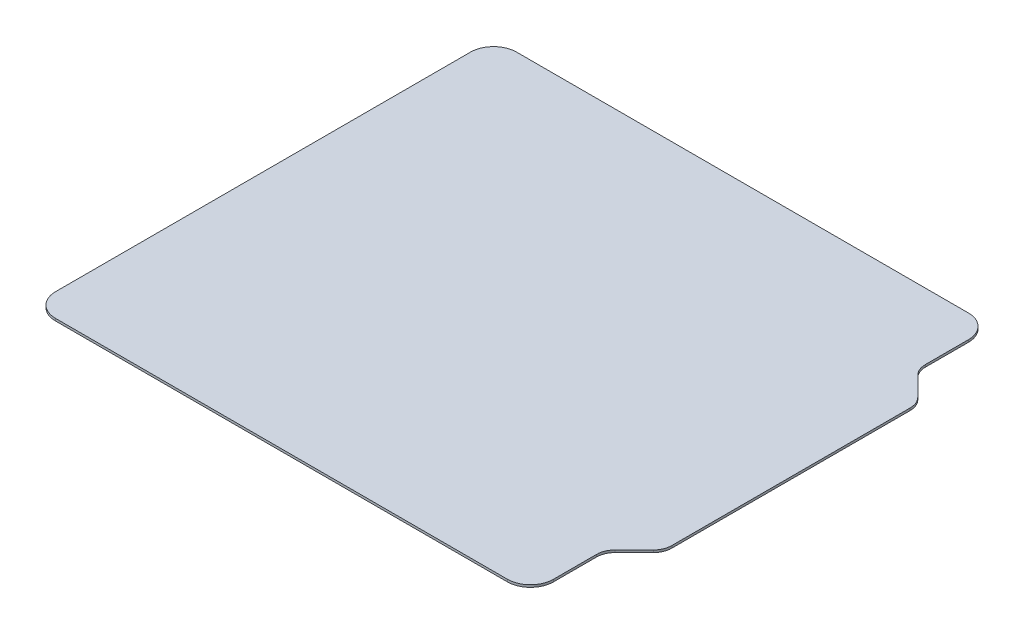
SolidWorks part; units mm, degrees
material "AISI 1020 Steel, Cold Rolled"
ref_plane "Front Plane" through (0, 0, 0) normal (0, 0, 1) x (1, 0, 0)
ref_plane "Top Plane" through (0, 0, 0) normal (0, 1, 0) x (1, 0, 0)
ref_plane "Right Plane" through (0, 0, 0) normal (1, 0, 0) x (0, 0, -1)
sketch "Sketch1" plane through (0, 0, 0) normal (0, 1, 0) x (1, 0, 0)
  line L1 (-114.5, 100) -> (114.5, 100)
  line L2 (-114.5, 100) -> (-114.5, -100)
  line L3 (-114.5, -100) -> (114.5, -100)
  line L4 (114.5, 100) -> (114.5, -100)
  line L5 (-114.5, 100) -> (114.5, -100) construction
  line L6 (-114.5, -100) -> (114.5, 100) construction
  point P0 (0, 0)
  dimension "D1" = 229
  dimension "D2" = 200
extrude "Boss-Extrude1" add sketch "Sketch1" along normal blind 1
sketch "Sketch2" plane through (0, 1, 0) normal (0, 1, 0) x (1, 0, 0)
  line L0 (114.5, 55) -> (101.5, 68)
  line L1 (114.5, -100) -> (114.5, 100) construction
  line L2 (101.5, 68) -> (101.5, 100)
  line L3 (114.5, 100) -> (-114.5, 100) construction
  line L4 (101.5, 100) -> (114.5, 100)
  line L5 (114.5, 100) -> (114.5, 55)
  line L6 (-55, 0) -> (55, 0) construction
  line L7 (101.5, -100) -> (114.5, -100)
  line L8 (101.5, -68) -> (101.5, -100)
  line L9 (114.5, -55) -> (101.5, -68)
  line L10 (114.5, -100) -> (114.5, -55)
  dimension "D1" = 45
  dimension "D2" = 32
  dimension "D3" = 13
extrude "Cut-Extrude1" cut sketch "Sketch2" against normal through all
fillet "Fillet1" radius 8 4 edges at (101.5, 0.5, 68) (114.5, 0.5, 55) (114.5, 0.5, -55) (101.5, 0.5, -68)
fillet "Fillet2" radius 10 4 edges at (-114.5, 0.5, -100) (-114.5, 0.5, 100) (101.5, 0.5, 100) (101.5, 0.5, -100)
